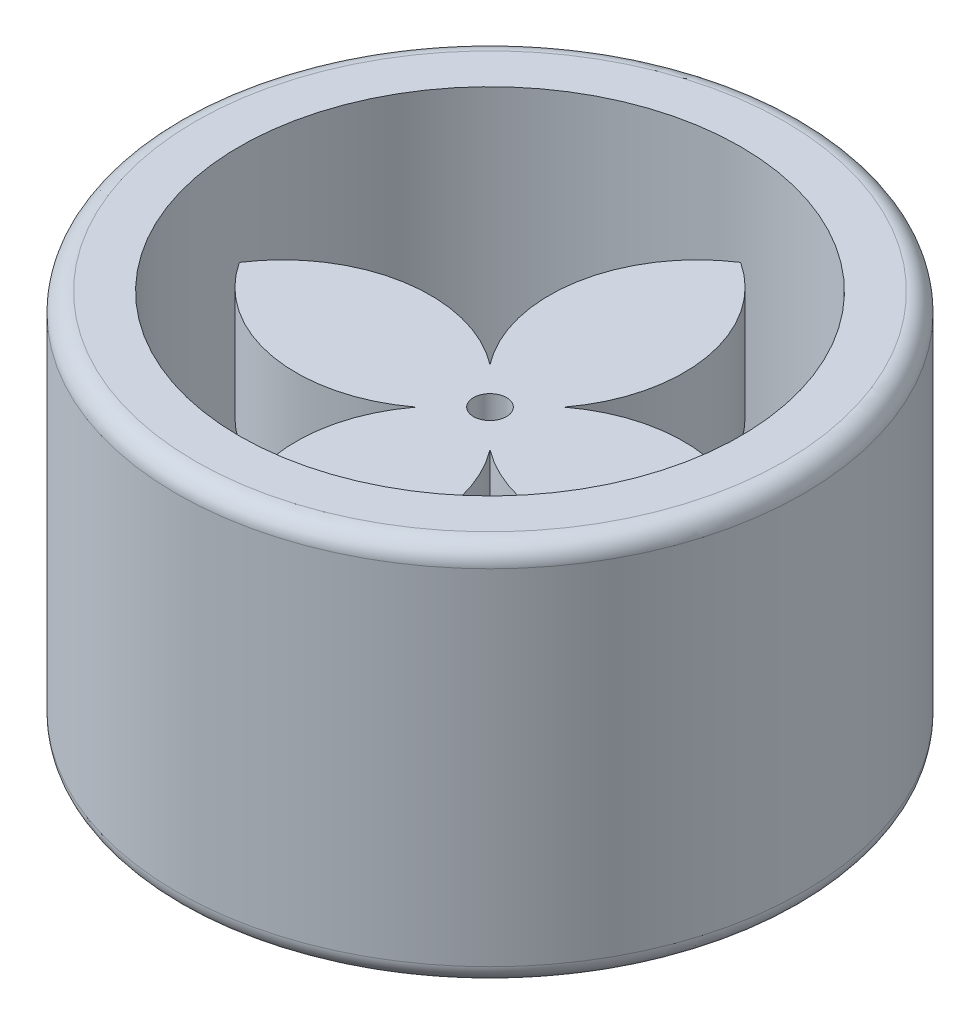
SolidWorks part; units mm, degrees
material "Rubber"
ref_plane "Front Plane" through (0, 0, 0) normal (0, 0, 1) x (1, 0, 0)
ref_plane "Top Plane" through (0, 0, 0) normal (0, 1, 0) x (1, 0, 0)
ref_plane "Right Plane" through (0, 0, 0) normal (1, 0, 0) x (0, 0, -1)
sketch "Sketch1" plane through (0, 0, 0) normal (0, 1, 0) x (1, 0, 0)
  line L0 (-2.635, 0) -> (50, 0) construction
  circle A0 centre (0, 0) radius 50
  circle A1 centre (0, 0) radius 2.635
  circle A2 centre (0, 0) radius 40
  arc A3 (5.877, 5.877) -> (40, 0) centre (20.2122, -12.8908) cw
  arc A4 (5.877, -5.877) -> (40, 0) centre (20.2122, 12.8908) ccw
  arc A5 (5.877, -5.877) -> (0, -40) centre (-12.8908, -20.2122) cw
  arc A6 (-5.877, -5.877) -> (0, -40) centre (12.8908, -20.2122) ccw
  arc A7 (-5.877, -5.877) -> (-40, 0) centre (-20.2122, 12.8908) cw
  arc A8 (-5.877, 5.877) -> (-40, 0) centre (-20.2122, -12.8908) ccw
  arc A9 (-5.877, 5.877) -> (0, 40) centre (12.8908, 20.2122) cw
  arc A10 (5.877, 5.877) -> (0, 40) centre (-12.8908, 20.2122) ccw
  circle A11 centre (0, 0) radius 8.3114 construction
  point P36 (0, 0)
  dimension "D1" = 100
  dimension "D2" = 5.27
  dimension "D3" = 10
  dimension "D4" = 4
  dimension "D5" = 23.6163
  dimension "D6" = 16.6228
extrude "Boss-Extrude1" add sketch "Sketch1" along normal blind 61 contours A2 A0 A8 region at (-48.5858, 0, 0)
extrude "Boss-Extrude2" add sketch "Sketch1<3>" along normal offset from surface (18 mm away) 16 from offset 27 separate body contours A1 A3 A10 A9 A8 A7 A6 A5 A4 region at (24.0286, 0, 9.2679) up to face at (0, 61, 40)
sketch "Sketch1<3>" plane through (0, 0, 0) normal (0, 1, 0) x (1, 0, 0) same geometry as "Sketch1"
fillet "Fillet1" radius 3 2 edges at (0, 61, 50) (0, 0, 50)
